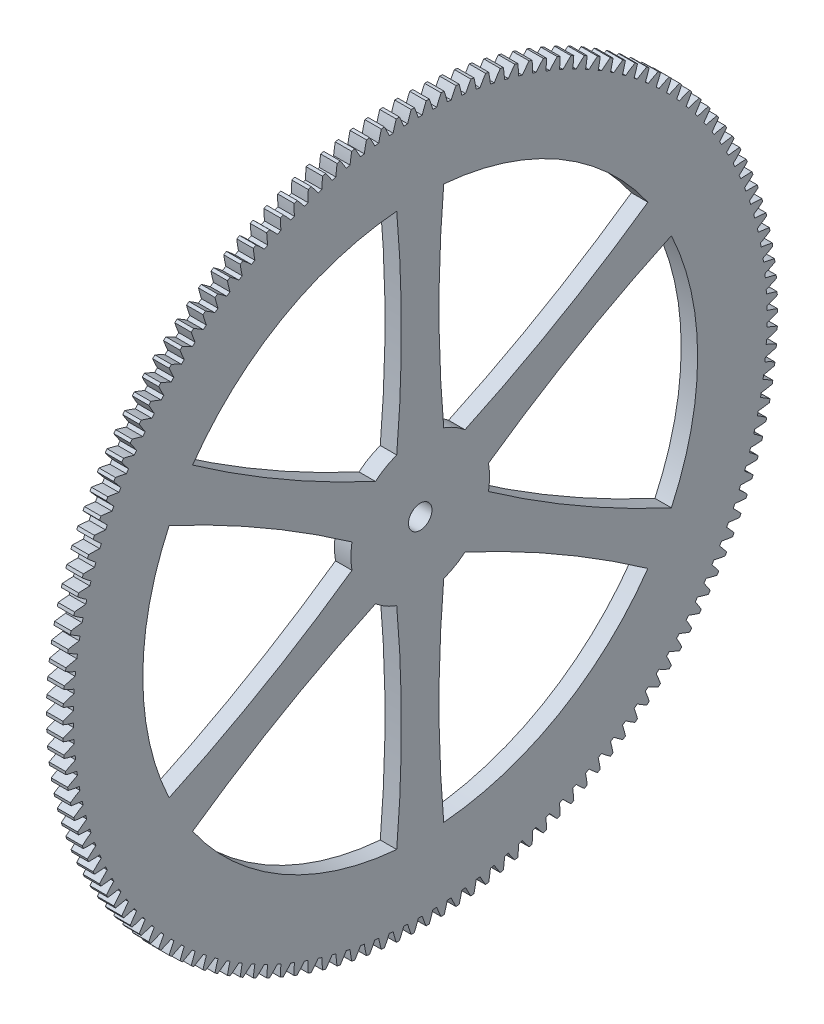
SolidWorks part; units mm, degrees
material "Cedar"
ref_plane "Plane1" through (0, 0, 0) normal (0, 0, 1) x (1, 0, 0)
ref_plane "Plane2" through (0, 0, 0) normal (0, 1, 0) x (1, 0, 0)
ref_plane "Plane3" through (0, 0, 0) normal (1, 0, 0) x (0, 0, -1)
sketch "HoldingSke" plane through (0, 0, 0) normal (0, 1, 0) x (1, 0, 0)
  line L0 (0, 0) -> (-439.9409, -254)
  line L1 (-15, 0) -> (100, 0) construction
  line L2 (0, 0) -> (-2.1039, 2.3779)
  line L3 (0, 0) -> (-11.863, 4.5341)
  line L4 (0, 0) -> (-7.479, 4.318)
  line L5 (0, 0) -> (-47.5972, -17.7524)
  line L6 (0, 0) -> (-3.6847, -2.4861)
  line L7 (-2.1039, 2.3779) -> (8.8308, 51.9871)
  line L8 (-76.2, 54.61) -> (-69.596, 54.61)
  line L9 (-71.009, 38.7566) -> (-53.1078, 45.2721)
  line L10 (-76.2, 71.12) -> (104.1128, 71.12)
  line L11 (0, 0) -> (-4.445, 0)
  line L12 (-76.2, 101.6) -> (-76.1492, 101.6)
  line L13 (24.9733, 27.94) -> (52.9518, 28.4284)
  line L14 (24.9733, 27.94) -> (25.0241, 27.9398)
  line L15 (24.9733, 27.94) -> (100.4021, 29.52)
  circle A0 centre (0, 0) radius 3.175
  circle A1 centre (0, 0) radius 38.1
  circle A2 centre (0, 0) radius 38.1
  circle A3 centre (0, 0) radius 3.175
  dimension "MHD" = 76.2
  dimension "Hub_dia" = 76.2
  dimension "Bore" = 6.35
  dimension "MBD" = 6.35
  dimension "Num_teeth" = 150
  dimension "Pitch_radius" = 180.3128
  dimension "Pitch" = 508
  dimension "Width" = 4.445
  dimension "Overall_len" = 50.8
  dimension "Show_teeth" = 150
  dimension "Thickness" = 4.445
  dimension "OAL" = 50.8001
  dimension "T_dim" = 6.604
  dimension "Ap" = 20
  dimension "H" = 19.05
  dimension "Backlash" = 0.0508
  dimension "Addendum_fac" = 1
  dimension "Dedendum_fac" = 1.2
  dimension "Clearance_fac" = 0.2
  dimension "Dedendum_add" = 0.0508
sketch "BasProSke" plane through (0, 0, 0) normal (0, 1, 0) x (1, 0, 0)
  line L0 (-10, 0) -> (60, 0) construction
  line L1 (0, 0) -> (0, 96.52)
  line L2 (0, 0) -> (4.445, 0)
  line L3 (4.445, 0) -> (4.445, 96.52)
  line L4 (4.445, 96.52) -> (0, 96.52)
  dimension "Diameter" = 193.04
  dimension "Thickness" = 4.445
revolve "Base-Revolve" add sketch "BasProSke" angle 360 about L0
sketch "TooCutSke" plane through (0, 0, 0) normal (1, 0, 0) x (0, 0, -1)
  line L1 (0, 0) -> (0, 107) construction
  line L2 (0, 0) -> (-1.0863, 95.2438) construction
  line L3 (0, 0) -> (-3.9893, 190.4496) construction
  line L4 (-1.0863, 95.2438) -> (-1.9947, 95.2248) construction
  arc A0 (0.5255, 93.6737) -> (-0.5255, 93.6737) centre (0, 0) ccw
  arc A1 (1.6056, 96.532) -> (-1.6056, 96.532) centre (0, 0) ccw
  circle A2 centre (0, 0) radius 95.25 construction
  circle A3 centre (0, 0) radius 89.5057 construction
  arc A4 (-0.5255, 93.6737) -> (-1.6056, 96.532) centre (-36.6772, 81.6459) ccw
  arc A5 (1.6056, 96.532) -> (0.5255, 93.6737) centre (36.6772, 81.6459) ccw
  dimension "Root_dia" = 187.3504
  dimension "Overcut_dia" = 193.0908
  dimension "Pitch_dia" = 190.5
  dimension "Base_dia" = 179.0114
  dimension "Flank_rad" = 38.1
  dimension "Half_ang" = 1.2
  dimension "Half_CT" = 0.9085
extrude "ToothCut" cut sketch "TooCutSke" along normal through all
fillet "Breaks" [suppressed] radius 0.0254 tangent propagation no
fillet "RootFillets" [suppressed] radius 0.3048
pattern_circular "TeethCuts" count 150 every 2.4 about axis through (-10, 0, 0) along (1, 0, 0) of "ToothCut", "RootFillets", "Breaks"
sketch "HubNeaOneSke" plane through (0, 0, 0) normal (-1, 0, 0) x (0, 0, 1)
  circle A0 centre (0, 0) radius 38.1
  dimension "Diameter" = 76.2
extrude "HubNearOne" [suppressed] add sketch "HubNeaOneSke" along normal blind 46.3551
sketch "HubNeaBotSke" plane through (0, 0, 0) normal (-1, 0, 0) x (0, 0, 1)
  circle A0 centre (0, 0) radius 38.1
  dimension "Diameter" = 76.2
extrude "HubNearBoth" [suppressed] add sketch "HubNeaBotSke" along normal blind 23.1775
ref_plane "FarPln" through (4.445, 0, 0) normal (1, 0, 0) x (0, 0, -1)
sketch "HubFarSke" plane through (4.445, 0, 0) normal (1, 0, 0) x (0, 0, -1)
  circle A0 centre (0, 0) radius 38.1
  dimension "Diameter" = 76.2
extrude "HubFar" [suppressed] add sketch "HubFarSke" along normal blind 23.1775
sketch "BorSke" plane through (0, 0, 0) normal (1, 0, 0) x (0, 0, -1)
  circle A0 centre (0, 0) radius 3.175
  dimension "Diameter" = 6.35
extrude "Bore" cut sketch "BorSke" along normal mid plane 101.6001
sketch "KeySke" plane through (0, 0, 0) normal (1, 0, 0) x (0, 0, -1)
  line L0 (-0.127, 0) -> (-0.127, 3.429)
  line L1 (-0.127, 3.429) -> (0.127, 3.429)
  line L2 (0.127, 3.429) -> (0.127, 0)
  line L3 (0, 0) -> (0, 34) construction
  line L4 (-0.127, 0) -> (0.127, 0)
  dimension "Offset" = 3.429
  dimension "Width" = 0.254
extrude "Keyway" [suppressed] cut sketch "KeySke" along normal mid plane 101.6001
pattern_circular "Keyway2" [suppressed] count 2 every 90 about axis through (-10, 0, 0) along (1, 0, 0)
sketch "Sketch1" plane through (4.445, 0, 0) normal (1, 0, 0) x (0, 0, -1)
  circle A0 centre (0, 0) radius 95.25
  dimension "D1" = 190.5
sketch "Sketch2" plane through (4.445, 0, 0) normal (1, 0, 0) x (0, 0, -1)
  line L0 (-6.35, 74.6706) -> (-6.35, 17.6261)
  line L1 (-6.35, 74.6706) -> (6.35, 74.6706)
  line L2 (-6.35, 17.6261) -> (6.35, 17.6261)
  line L3 (6.35, 74.6706) -> (6.35, 17.6261)
  circle A0 centre (0, 0) radius 18.735
  circle A1 centre (0, 0) radius 74.9402
  arc A2 (-6.35, 17.6261) -> (-6.35, 74.6706) centre (-325.9985, 46.1484) ccw
  arc A3 (6.35, 17.6261) -> (6.35, 74.6706) centre (325.9985, 46.1484) cw
  arc A4 (18.4396, 3.3138) -> (67.8417, 31.8361) centre (202.9649, -259.2488) cw
  arc A5 (12.0896, 14.3123) -> (61.4917, 42.8346) centre (-123.0336, 305.3972) ccw
  arc A6 (12.0896, -14.3123) -> (61.4917, -42.8346) centre (-123.0336, -305.3972) cw
  arc A7 (18.4396, -3.3138) -> (67.8417, -31.8361) centre (202.9649, 259.2488) ccw
  arc A8 (-6.35, -17.6261) -> (-6.35, -74.6706) centre (-325.9985, -46.1484) cw
  arc A9 (6.35, -17.6261) -> (6.35, -74.6706) centre (325.9985, -46.1484) ccw
  arc A10 (-18.4396, -3.3138) -> (-67.8417, -31.8361) centre (-202.9649, 259.2488) cw
  arc A11 (-12.0896, -14.3123) -> (-61.4917, -42.8346) centre (123.0336, -305.3972) ccw
  arc A12 (-12.0896, 14.3123) -> (-61.4917, 42.8346) centre (123.0336, 305.3972) cw
  arc A13 (-18.4396, 3.3138) -> (-67.8417, 31.8361) centre (-202.9649, -259.2488) ccw
  point P8 (-5.08, 46.1484)
  point P9 (5.08, 46.1484)
  point P45 (0, 0)
  dimension "D1" = 149.8803
  dimension "D2" = 37.4701
  dimension "D4" = 10.16
  dimension "D3" = 12.7
  dimension "D5" = 6
extrude "Cut-Extrude1" cut sketch "Sketch2" against normal through all contours A12 A0 L0 A1 | A0 A5 A1 L3 | A0 A7 A1 A4 | A0 A9 A1 A6 | A0 A11 A1 A8 | A0 A13 A1 A10 | L0 A2 | A3 L3 region at (4.445, 46.1484, 5.8419) region at (4.445, 45.4509, 26.7225) region at (4.445, 45.4509, -26.7225) region at (4.445, 46.1484, -5.8419) region at (4.445, 0, 52.5004) region at (4.445, 0, -52.5004) region at (4.445, -45.4667, 26.2502) region at (4.445, -45.4667, -26.2502)
equation "' \"Pitch@HoldingSke\" = 4"
equation "' \"Num_teeth@HoldingSke\" = 12"
equation "' \"Ap@HoldingSke\" =  20"
equation "' \"Width@HoldingSke\" = 0.5"
equation "' \"Hub_dia@HoldingSke\"= 1"
equation "' \"Overall_len@HoldingSke\" = 1.0"
equation "' \"Bore@HoldingSke\" = 0.75"
equation "' \"T_dim@HoldingSke\" = 0.85"
equation "' \"Width@KeySke\" = 0.25"
equation "' \"Show_teeth@HoldingSke\" = 13"
equation "' \"Backlash@HoldingSke\" = 0.009"
equation "' \"Addendum_fac@HoldingSke\" = 1.0"
equation "' \"Dedendum_fac@HoldingSke\" = 1.25"
equation "' \"Dedendum_add@HoldingSke\" = 0.00005"
equation "' \"Clearance_fac@HoldingSke\" = 0.25"
equation "' \"Pitch@HoldingSke\" = 0.5"
equation "' \"Num_teeth@HoldingSke\" = 23"
equation "' \"Show_teeth@HoldingSke\" = 23"
equation "' \"Backlash@HoldingSke\" = 0.0375"
equation "\"Overcut_dia@TooCutSke\" = (\"Num_teeth@HoldingSke\" + 2 * \"Addendum_fac@HoldingSke\") / \"Pitch@HoldingSke\" + 0.002"
equation "\"Pitch_dia@TooCutSke\" = \"Num_teeth@HoldingSke\" / \"Pitch@HoldingSke\""
equation "\"Base_dia@TooCutSke\" = \"Num_teeth@HoldingSke\" / \"Pitch@HoldingSke\" * cos((\"Ap@HoldingSke\"  * 3.14159265 / 180))"
equation "\"Root_dia@TooCutSke\" = (\"Num_teeth@HoldingSke\" + 2) / \"Pitch@HoldingSke\" - 2 * (\"Addendum_fac@HoldingSke\" + \"Dedendum_fac@HoldingSke\") / \"Pitch@HoldingSke\" - \"Dedendum_add@HoldingSke\" * 2"
equation "\"Half_ang@TooCutSke\" = 180 / \"Num_teeth@HoldingSke\""
equation "\"Half_CT@TooCutSke\" = \"Num_teeth@HoldingSke\" / \"Pitch@HoldingSke\" * sin((3.14159265 / 2 / \"Num_teeth@HoldingSke\")) / 2 - 7 * \"Backlash@HoldingSke\" / 4"
equation "\"Flank_rad@TooCutSke\" = \"Num_teeth@HoldingSke\" / \"Pitch@HoldingSke\" / 5"
equation "\"Radius@RootFillets\" = \"Clearance_fac@HoldingSke\" / \"Pitch@HoldingSke\" + \"Dedendum_add@HoldingSke\""
equation "\"Break_rad@Breaks\" = 0.02 / \"Pitch@HoldingSke\""
equation "\"Thickness@HoldingSke\" = \"Width@HoldingSke\""
equation "\"OAL@HoldingSke\" = \"Thickness@HoldingSke\""
equation "\"MHD@HoldingSke\" = (\"Num_teeth@HoldingSke\" + 2) / \"Pitch@HoldingSke\" - 2 * (\"Addendum_fac@HoldingSke\" + \"Dedendum_fac@HoldingSke\")  / \"Pitch@HoldingSke\" - \"Dedendum_add@HoldingSke\" * 2"
equation "\"MBD@HoldingSke\" = (\"Num_teeth@HoldingSke\" + 2) / \"Pitch@HoldingSke\" - 2 * (\"Addendum_fac@HoldingSke\" + \"Dedendum_fac@HoldingSke\")  / \"Pitch@HoldingSke\" - \"Dedendum_add@HoldingSke\" * 2 - 0.002"
equation "\"MHD@HoldingSke\" = ((sgn( \"MHD@HoldingSke\" - \"Hub_dia@HoldingSke\" )-1)*( \"MHD@HoldingSke\" - \"Hub_dia@HoldingSke\" ))/-2+ \"Hub_dia@HoldingSke\""
equation "\"MBD@HoldingSke\" = ((sgn( \"MBD@HoldingSke\" - \"Bore@HoldingSke\" )-1)*( \"MBD@HoldingSke\" - \"Bore@HoldingSke\" ))/-2+ \"Bore@HoldingSke\""
equation "\"OAL@HoldingSke\" = ((sgn( \"OAL@HoldingSke\" - \"Overall_len@HoldingSke\" )+1)*( \"OAL@HoldingSke\" - \"Overall_len@HoldingSke\" ))/2 + \"Overall_len@HoldingSke\" + 0.000002"
equation "\"Num_teeth@TeethCuts\" = int( \"Show_teeth@HoldingSke\" ) + 1"
equation "\"Num_teeth@TeethCuts\" = ((sgn( \"Num_teeth@TeethCuts\" - \"Num_teeth@HoldingSke\" )-1)*( \"Num_teeth@TeethCuts\" - \"Num_teeth@HoldingSke\" ))/-2+ \"Num_teeth@HoldingSke\""
equation "\"Num_teeth@TeethCuts\" = ((sgn( \"Num_teeth@TeethCuts\" - 2.0)+1)*( \"Num_teeth@TeethCuts\" - 2.0))/2 +2.0"
equation "\"Angle@TeethCuts\" = 360.0 / \"Num_teeth@HoldingSke\""
equation "\"Diameter@BasProSke\" = (\"Num_teeth@HoldingSke\" + 2 * \"Addendum_fac@HoldingSke\") / \"Pitch@HoldingSke\""
equation "\"Thickness@BasProSke\"  = \"Thickness@HoldingSke\""
equation "' \"Fillet_rad@BasProSke\" =  \"Thickness@HoldingSke\" * 0.05"
equation "\"MHD@HoldingSke\" = ((sgn( \"MHD@HoldingSke\" - \"Root_dia@TooCutSke\" )-1)*( \"MHD@HoldingSke\" - \"Root_dia@TooCutSke\" ))/-2+ \"Root_dia@TooCutSke\""
equation "\"Diameter@HubNeaOneSke\" = \"MHD@HoldingSke\""
equation "\"Length@HubNearOne\" = \"OAL@HoldingSke\" - \"Thickness@BasProSke\""
equation "\"Diameter@HubNeaBotSke\" = \"MHD@HoldingSke\""
equation "\"Length@HubNearBoth\" = ( \"OAL@HoldingSke\" - \"Thickness@BasProSke\" ) / 2.0"
equation "\"Thickness@FarPln\" = \"Thickness@BasProSke\""
equation "\"Diameter@HubFarSke\" = \"MHD@HoldingSke\""
equation "\"Length@HubFar\" = ( \"OAL@HoldingSke\" - \"Thickness@BasProSke\" ) / 2.0"
equation "\"Diameter@BorSke\" = \"MBD@HoldingSke\""
equation "\"D1@Bore\" = \"OAL@HoldingSke\" * 2.0"
equation "\"D1@Keyway\" = \"OAL@HoldingSke\" * 2.0"
equation "\"Offset@KeySke\" = \"T_dim@HoldingSke\" - \"MBD@HoldingSke\" / 2.0"
